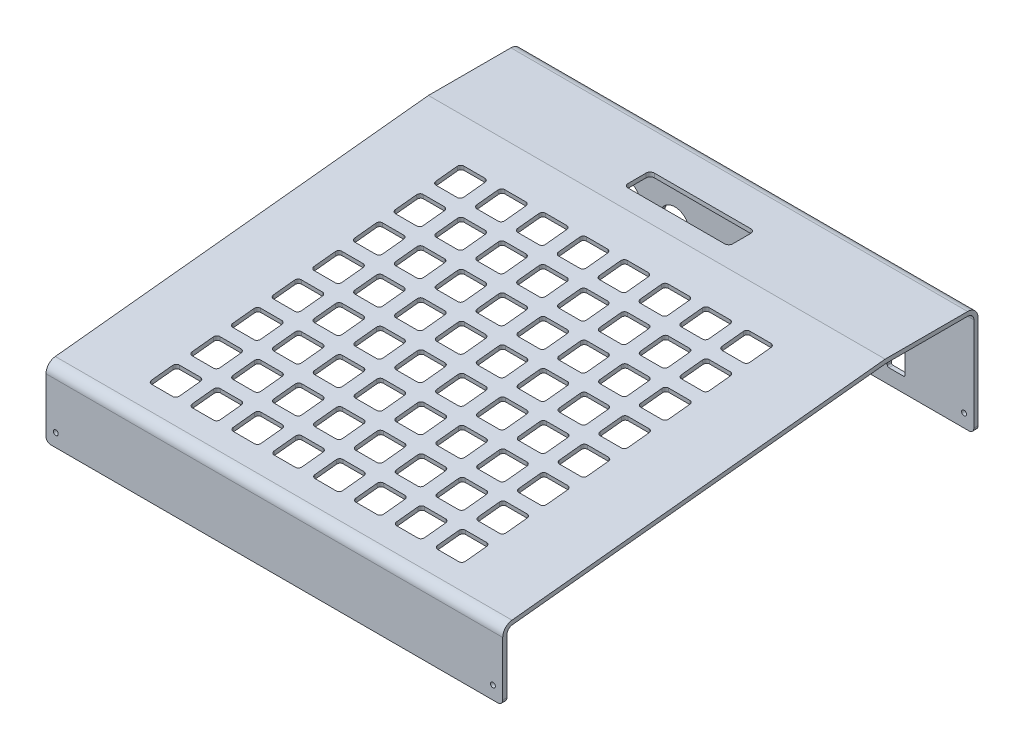
SolidWorks part; units mm, degrees
material "Acrylic (Medium-high impact)"
ref_plane "Front Plane" through (0, 0, 0) normal (0, 0, 1) x (1, 0, 0)
ref_plane "Top Plane" through (0, 0, 0) normal (0, 1, 0) x (1, 0, 0)
ref_plane "Right Plane" through (0, 0, 0) normal (1, 0, 0) x (0, 0, -1)
sketch "Sketch1" plane through (0, 0, 0) normal (1, 0, 0) x (0, 0, -1)
  line L0 (0, 0) -> (0, 84.1309) construction
  line L1 (0, 0) -> (161.7203, 0) construction
  line L2 (-166.9735, -57.6462) -> (123.786, -57.6462)
  line L3 (130.136, -51.2962) -> (130.136, 12.2038)
  line L4 (123.786, 18.5538) -> (66.9711, 18.5538)
  line L5 (66.3027, 18.5185) -> (-167.6419, -6.2448)
  line L6 (-173.3235, -12.5596) -> (-173.3235, -51.2962)
  arc A0 (66.3027, 18.5185) -> (66.9711, 18.5538) centre (66.9711, 12.2038) cw
  arc A1 (123.786, 18.5538) -> (130.136, 12.2038) centre (123.786, 12.2038) cw
  arc A2 (130.136, -51.2962) -> (123.786, -57.6462) centre (123.786, -51.2962) cw
  arc A3 (-166.9735, -57.6462) -> (-173.3235, -51.2962) centre (-166.9735, -51.2962) cw
  arc A4 (-173.3235, -12.5596) -> (-167.6419, -6.2448) centre (-166.9735, -12.5596) cw
  point P11 (66.636, 18.5538)
  point P14 (130.136, 18.5538)
  point P17 (130.136, -57.6462)
  point P20 (-173.3235, -57.6462)
  point P23 (-173.3235, -6.8462)
  dimension "D5" = 6.35
  dimension "D1" = 241.3
  dimension "D2" = 63.5
  dimension "D3" = 76.2
  dimension "D4" = 50.8
sketch "Sketch2" plane through (0, 0, 0) normal (1, 0, 0) x (0, 0, -1)
  line L0 (-166.9735, -54.4712) -> (-166.9735, -18.2729)
  line L1 (-161.2919, -11.9581) -> (66.9711, 12.2038)
  line L2 (66.9711, 12.2038) -> (117.436, 12.2038)
  line L3 (123.786, 5.8538) -> (123.786, -54.4712)
  arc A0 (-161.2919, -11.9581) -> (-166.9735, -18.2729) centre (-160.6235, -18.2729) ccw
  arc A1 (123.786, 5.8538) -> (117.436, 12.2038) centre (117.436, 5.8538) ccw
  point P12 (-166.9735, -12.5596)
  point P15 (123.786, 12.2038)
  dimension "D1" = 6.35
extrude "Extrude-Thin1" add sketch "Sketch2" along normal blind 279.4 thin thin type one direction wall 2.54
sketch "Sketch3" plane through (0, 5.0581, 0.5354) normal (0, 0.9944, 0.1053) x (1, 0, 0)
  line L0 (70.5895, 43.7288) -> (83.5895, 43.7288)
  line L1 (68.5895, 41.7288) -> (68.5895, 28.7288)
  line L2 (45.5895, 43.7288) -> (58.5895, 43.7288)
  line L3 (43.5895, 41.7288) -> (43.5895, 28.7288)
  line L4 (45.5895, 26.7288) -> (58.5895, 26.7288)
  line L5 (70.5895, 26.7288) -> (83.5895, 26.7288)
  line L6 (60.5895, 41.7288) -> (60.5895, 28.7288)
  line L7 (43.5895, 43.7288) -> (60.5895, 26.7288) construction
  line L8 (43.5895, 26.7288) -> (60.5895, 43.7288) construction
  line L9 (85.5895, 41.7288) -> (85.5895, 28.7288)
  line L10 (95.5895, 43.7288) -> (108.5895, 43.7288)
  line L11 (93.5895, 41.7288) -> (93.5895, 28.7288)
  line L12 (95.5895, 26.7288) -> (108.5895, 26.7288)
  line L13 (110.5895, 41.7288) -> (110.5895, 28.7288)
  line L14 (120.5895, 43.7288) -> (133.5895, 43.7288)
  line L15 (118.5895, 41.7288) -> (118.5895, 28.7288)
  line L16 (120.5895, 26.7288) -> (133.5895, 26.7288)
  line L17 (135.5895, 41.7288) -> (135.5895, 28.7288)
  line L18 (145.5895, 43.7288) -> (158.5895, 43.7288)
  line L19 (143.5895, 41.7288) -> (143.5895, 28.7288)
  line L20 (145.5895, 26.7288) -> (158.5895, 26.7288)
  line L21 (160.5895, 41.7288) -> (160.5895, 28.7288)
  line L22 (170.5895, 43.7288) -> (183.5895, 43.7288)
  line L23 (168.5895, 41.7288) -> (168.5895, 28.7288)
  line L24 (170.5895, 26.7288) -> (183.5895, 26.7288)
  line L25 (185.5895, 41.7288) -> (185.5895, 28.7288)
  line L26 (195.5895, 43.7288) -> (208.5895, 43.7288)
  line L27 (193.5895, 41.7288) -> (193.5895, 28.7288)
  line L28 (195.5895, 26.7288) -> (208.5895, 26.7288)
  line L29 (210.5895, 41.7288) -> (210.5895, 28.7288)
  line L30 (220.5895, 43.7288) -> (233.5895, 43.7288)
  line L31 (218.5895, 41.7288) -> (218.5895, 28.7288)
  line L32 (220.5895, 26.7288) -> (233.5895, 26.7288)
  line L33 (235.5895, 41.7288) -> (235.5895, 28.7288)
  line L34 (70.5895, 18.7288) -> (83.5895, 18.7288)
  line L35 (68.5895, 16.7288) -> (68.5895, 3.7288)
  line L36 (70.5895, 1.7288) -> (83.5895, 1.7288)
  line L37 (85.5895, 16.7288) -> (85.5895, 3.7288)
  line L38 (95.5895, 18.7288) -> (108.5895, 18.7288)
  line L39 (93.5895, 16.7288) -> (93.5895, 3.7288)
  line L40 (95.5895, 1.7288) -> (108.5895, 1.7288)
  line L41 (110.5895, 16.7288) -> (110.5895, 3.7288)
  line L42 (120.5895, 18.7288) -> (133.5895, 18.7288)
  line L43 (118.5895, 16.7288) -> (118.5895, 3.7288)
  line L44 (120.5895, 1.7288) -> (133.5895, 1.7288)
  line L45 (135.5895, 16.7288) -> (135.5895, 3.7288)
  line L46 (145.5895, 18.7288) -> (158.5895, 18.7288)
  line L47 (143.5895, 16.7288) -> (143.5895, 3.7288)
  line L48 (145.5895, 1.7288) -> (158.5895, 1.7288)
  line L49 (160.5895, 16.7288) -> (160.5895, 3.7288)
  line L50 (170.5895, 18.7288) -> (183.5895, 18.7288)
  line L51 (168.5895, 16.7288) -> (168.5895, 3.7288)
  line L52 (170.5895, 1.7288) -> (183.5895, 1.7288)
  line L53 (185.5895, 16.7288) -> (185.5895, 3.7288)
  line L54 (195.5895, 18.7288) -> (208.5895, 18.7288)
  line L55 (193.5895, 16.7288) -> (193.5895, 3.7288)
  line L56 (195.5895, 1.7288) -> (208.5895, 1.7288)
  line L57 (210.5895, 16.7288) -> (210.5895, 3.7288)
  line L58 (220.5895, 18.7288) -> (233.5895, 18.7288)
  line L59 (218.5895, 16.7288) -> (218.5895, 3.7288)
  line L60 (220.5895, 1.7288) -> (233.5895, 1.7288)
  line L61 (235.5895, 16.7288) -> (235.5895, 3.7288)
  line L62 (70.5895, -6.2712) -> (83.5895, -6.2712)
  line L63 (68.5895, -8.2712) -> (68.5895, -21.2712)
  line L64 (70.5895, -23.2712) -> (83.5895, -23.2712)
  line L65 (85.5895, -8.2712) -> (85.5895, -21.2712)
  line L66 (95.5895, -6.2712) -> (108.5895, -6.2712)
  line L67 (93.5895, -8.2712) -> (93.5895, -21.2712)
  line L68 (95.5895, -23.2712) -> (108.5895, -23.2712)
  line L69 (110.5895, -8.2712) -> (110.5895, -21.2712)
  line L70 (120.5895, -6.2712) -> (133.5895, -6.2712)
  line L71 (118.5895, -8.2712) -> (118.5895, -21.2712)
  line L72 (120.5895, -23.2712) -> (133.5895, -23.2712)
  line L73 (135.5895, -8.2712) -> (135.5895, -21.2712)
  line L74 (145.5895, -6.2712) -> (158.5895, -6.2712)
  line L75 (143.5895, -8.2712) -> (143.5895, -21.2712)
  line L76 (145.5895, -23.2712) -> (158.5895, -23.2712)
  line L77 (160.5895, -8.2712) -> (160.5895, -21.2712)
  line L78 (170.5895, -6.2712) -> (183.5895, -6.2712)
  line L79 (168.5895, -8.2712) -> (168.5895, -21.2712)
  line L80 (170.5895, -23.2712) -> (183.5895, -23.2712)
  line L81 (185.5895, -8.2712) -> (185.5895, -21.2712)
  line L82 (195.5895, -6.2712) -> (208.5895, -6.2712)
  line L83 (193.5895, -8.2712) -> (193.5895, -21.2712)
  line L84 (195.5895, -23.2712) -> (208.5895, -23.2712)
  line L85 (210.5895, -8.2712) -> (210.5895, -21.2712)
  line L86 (220.5895, -6.2712) -> (233.5895, -6.2712)
  line L87 (218.5895, -8.2712) -> (218.5895, -21.2712)
  line L88 (220.5895, -23.2712) -> (233.5895, -23.2712)
  line L89 (235.5895, -8.2712) -> (235.5895, -21.2712)
  line L90 (70.5895, -31.2712) -> (83.5895, -31.2712)
  line L91 (68.5895, -33.2712) -> (68.5895, -46.2712)
  line L92 (70.5895, -48.2712) -> (83.5895, -48.2712)
  line L93 (85.5895, -33.2712) -> (85.5895, -46.2712)
  line L94 (95.5895, -31.2712) -> (108.5895, -31.2712)
  line L95 (93.5895, -33.2712) -> (93.5895, -46.2712)
  line L96 (95.5895, -48.2712) -> (108.5895, -48.2712)
  line L97 (110.5895, -33.2712) -> (110.5895, -46.2712)
  line L98 (120.5895, -31.2712) -> (133.5895, -31.2712)
  line L99 (118.5895, -33.2712) -> (118.5895, -46.2712)
  line L100 (120.5895, -48.2712) -> (133.5895, -48.2712)
  line L101 (135.5895, -33.2712) -> (135.5895, -46.2712)
  line L102 (145.5895, -31.2712) -> (158.5895, -31.2712)
  line L103 (143.5895, -33.2712) -> (143.5895, -46.2712)
  line L104 (145.5895, -48.2712) -> (158.5895, -48.2712)
  line L105 (160.5895, -33.2712) -> (160.5895, -46.2712)
  line L106 (170.5895, -31.2712) -> (183.5895, -31.2712)
  line L107 (168.5895, -33.2712) -> (168.5895, -46.2712)
  line L108 (170.5895, -48.2712) -> (183.5895, -48.2712)
  line L109 (185.5895, -33.2712) -> (185.5895, -46.2712)
  line L110 (195.5895, -31.2712) -> (208.5895, -31.2712)
  line L111 (193.5895, -33.2712) -> (193.5895, -46.2712)
  line L112 (195.5895, -48.2712) -> (208.5895, -48.2712)
  line L113 (210.5895, -33.2712) -> (210.5895, -46.2712)
  line L114 (220.5895, -31.2712) -> (233.5895, -31.2712)
  line L115 (218.5895, -33.2712) -> (218.5895, -46.2712)
  line L116 (220.5895, -48.2712) -> (233.5895, -48.2712)
  line L117 (235.5895, -33.2712) -> (235.5895, -46.2712)
  line L118 (70.5895, -56.2712) -> (83.5895, -56.2712)
  line L119 (68.5895, -58.2712) -> (68.5895, -71.2712)
  line L120 (70.5895, -73.2712) -> (83.5895, -73.2712)
  line L121 (85.5895, -58.2712) -> (85.5895, -71.2712)
  line L122 (95.5895, -56.2712) -> (108.5895, -56.2712)
  line L123 (93.5895, -58.2712) -> (93.5895, -71.2712)
  line L124 (95.5895, -73.2712) -> (108.5895, -73.2712)
  line L125 (110.5895, -58.2712) -> (110.5895, -71.2712)
  line L126 (120.5895, -56.2712) -> (133.5895, -56.2712)
  line L127 (118.5895, -58.2712) -> (118.5895, -71.2712)
  line L128 (120.5895, -73.2712) -> (133.5895, -73.2712)
  line L129 (135.5895, -58.2712) -> (135.5895, -71.2712)
  line L130 (145.5895, -56.2712) -> (158.5895, -56.2712)
  line L131 (143.5895, -58.2712) -> (143.5895, -71.2712)
  line L132 (145.5895, -73.2712) -> (158.5895, -73.2712)
  line L133 (160.5895, -58.2712) -> (160.5895, -71.2712)
  line L134 (170.5895, -56.2712) -> (183.5895, -56.2712)
  line L135 (168.5895, -58.2712) -> (168.5895, -71.2712)
  line L136 (170.5895, -73.2712) -> (183.5895, -73.2712)
  line L137 (185.5895, -58.2712) -> (185.5895, -71.2712)
  line L138 (195.5895, -56.2712) -> (208.5895, -56.2712)
  line L139 (193.5895, -58.2712) -> (193.5895, -71.2712)
  line L140 (195.5895, -73.2712) -> (208.5895, -73.2712)
  line L141 (210.5895, -58.2712) -> (210.5895, -71.2712)
  line L142 (220.5895, -56.2712) -> (233.5895, -56.2712)
  line L143 (218.5895, -58.2712) -> (218.5895, -71.2712)
  line L144 (220.5895, -73.2712) -> (233.5895, -73.2712)
  line L145 (235.5895, -58.2712) -> (235.5895, -71.2712)
  line L146 (70.5895, -81.2712) -> (83.5895, -81.2712)
  line L147 (68.5895, -83.2712) -> (68.5895, -96.2712)
  line L148 (70.5895, -98.2712) -> (83.5895, -98.2712)
  line L149 (85.5895, -83.2712) -> (85.5895, -96.2712)
  line L150 (95.5895, -81.2712) -> (108.5895, -81.2712)
  line L151 (93.5895, -83.2712) -> (93.5895, -96.2712)
  line L152 (95.5895, -98.2712) -> (108.5895, -98.2712)
  line L153 (110.5895, -83.2712) -> (110.5895, -96.2712)
  line L154 (120.5895, -81.2712) -> (133.5895, -81.2712)
  line L155 (118.5895, -83.2712) -> (118.5895, -96.2712)
  line L156 (120.5895, -98.2712) -> (133.5895, -98.2712)
  line L157 (135.5895, -83.2712) -> (135.5895, -96.2712)
  line L158 (145.5895, -81.2712) -> (158.5895, -81.2712)
  line L159 (143.5895, -83.2712) -> (143.5895, -96.2712)
  line L160 (145.5895, -98.2712) -> (158.5895, -98.2712)
  line L161 (160.5895, -83.2712) -> (160.5895, -96.2712)
  line L162 (170.5895, -81.2712) -> (183.5895, -81.2712)
  line L163 (168.5895, -83.2712) -> (168.5895, -96.2712)
  line L164 (170.5895, -98.2712) -> (183.5895, -98.2712)
  line L165 (185.5895, -83.2712) -> (185.5895, -96.2712)
  line L166 (195.5895, -81.2712) -> (208.5895, -81.2712)
  line L167 (193.5895, -83.2712) -> (193.5895, -96.2712)
  line L168 (195.5895, -98.2712) -> (208.5895, -98.2712)
  line L169 (210.5895, -83.2712) -> (210.5895, -96.2712)
  line L170 (220.5895, -81.2712) -> (233.5895, -81.2712)
  line L171 (218.5895, -83.2712) -> (218.5895, -96.2712)
  line L172 (220.5895, -98.2712) -> (233.5895, -98.2712)
  line L173 (235.5895, -83.2712) -> (235.5895, -96.2712)
  line L174 (70.5895, -106.2712) -> (83.5895, -106.2712)
  line L175 (68.5895, -108.2712) -> (68.5895, -121.2712)
  line L176 (70.5895, -123.2712) -> (83.5895, -123.2712)
  line L177 (85.5895, -108.2712) -> (85.5895, -121.2712)
  line L178 (95.5895, -106.2712) -> (108.5895, -106.2712)
  line L179 (93.5895, -108.2712) -> (93.5895, -121.2712)
  line L180 (95.5895, -123.2712) -> (108.5895, -123.2712)
  line L181 (110.5895, -108.2712) -> (110.5895, -121.2712)
  line L182 (120.5895, -106.2712) -> (133.5895, -106.2712)
  line L183 (118.5895, -108.2712) -> (118.5895, -121.2712)
  line L184 (120.5895, -123.2712) -> (133.5895, -123.2712)
  line L185 (135.5895, -108.2712) -> (135.5895, -121.2712)
  line L186 (145.5895, -106.2712) -> (158.5895, -106.2712)
  line L187 (143.5895, -108.2712) -> (143.5895, -121.2712)
  line L188 (145.5895, -123.2712) -> (158.5895, -123.2712)
  line L189 (160.5895, -108.2712) -> (160.5895, -121.2712)
  line L190 (170.5895, -106.2712) -> (183.5895, -106.2712)
  line L191 (168.5895, -108.2712) -> (168.5895, -121.2712)
  line L192 (170.5895, -123.2712) -> (183.5895, -123.2712)
  line L193 (185.5895, -108.2712) -> (185.5895, -121.2712)
  line L194 (195.5895, -106.2712) -> (208.5895, -106.2712)
  line L195 (193.5895, -108.2712) -> (193.5895, -121.2712)
  line L196 (195.5895, -123.2712) -> (208.5895, -123.2712)
  line L197 (210.5895, -108.2712) -> (210.5895, -121.2712)
  line L198 (220.5895, -106.2712) -> (233.5895, -106.2712)
  line L199 (218.5895, -108.2712) -> (218.5895, -121.2712)
  line L200 (220.5895, -123.2712) -> (233.5895, -123.2712)
  line L201 (235.5895, -108.2712) -> (235.5895, -121.2712)
  line L202 (70.5895, -131.2712) -> (83.5895, -131.2712)
  line L203 (68.5895, -133.2712) -> (68.5895, -146.2712)
  line L204 (70.5895, -148.2712) -> (83.5895, -148.2712)
  line L205 (85.5895, -133.2712) -> (85.5895, -146.2712)
  line L206 (95.5895, -131.2712) -> (108.5895, -131.2712)
  line L207 (93.5895, -133.2712) -> (93.5895, -146.2712)
  line L208 (95.5895, -148.2712) -> (108.5895, -148.2712)
  line L209 (110.5895, -133.2712) -> (110.5895, -146.2712)
  line L210 (120.5895, -131.2712) -> (133.5895, -131.2712)
  line L211 (118.5895, -133.2712) -> (118.5895, -146.2712)
  line L212 (120.5895, -148.2712) -> (133.5895, -148.2712)
  line L213 (135.5895, -133.2712) -> (135.5895, -146.2712)
  line L214 (145.5895, -131.2712) -> (158.5895, -131.2712)
  line L215 (143.5895, -133.2712) -> (143.5895, -146.2712)
  line L216 (145.5895, -148.2712) -> (158.5895, -148.2712)
  line L217 (160.5895, -133.2712) -> (160.5895, -146.2712)
  line L218 (170.5895, -131.2712) -> (183.5895, -131.2712)
  line L219 (168.5895, -133.2712) -> (168.5895, -146.2712)
  line L220 (170.5895, -148.2712) -> (183.5895, -148.2712)
  line L221 (185.5895, -133.2712) -> (185.5895, -146.2712)
  line L222 (195.5895, -131.2712) -> (208.5895, -131.2712)
  line L223 (193.5895, -133.2712) -> (193.5895, -146.2712)
  line L224 (195.5895, -148.2712) -> (208.5895, -148.2712)
  line L225 (210.5895, -133.2712) -> (210.5895, -146.2712)
  line L226 (220.5895, -131.2712) -> (233.5895, -131.2712)
  line L227 (218.5895, -133.2712) -> (218.5895, -146.2712)
  line L228 (220.5895, -148.2712) -> (233.5895, -148.2712)
  line L229 (235.5895, -133.2712) -> (235.5895, -146.2712)
  line L230 (45.5895, 18.7288) -> (58.5895, 18.7288)
  line L231 (43.5895, 16.7288) -> (43.5895, 3.7288)
  line L232 (45.5895, 1.7288) -> (58.5895, 1.7288)
  line L233 (60.5895, 16.7288) -> (60.5895, 3.7288)
  line L234 (45.5895, -6.2712) -> (58.5895, -6.2712)
  line L235 (43.5895, -8.2712) -> (43.5895, -21.2712)
  line L236 (45.5895, -23.2712) -> (58.5895, -23.2712)
  line L237 (60.5895, -8.2712) -> (60.5895, -21.2712)
  line L238 (45.5895, -31.2712) -> (58.5895, -31.2712)
  line L239 (43.5895, -33.2712) -> (43.5895, -46.2712)
  line L240 (45.5895, -48.2712) -> (58.5895, -48.2712)
  line L241 (60.5895, -33.2712) -> (60.5895, -46.2712)
  line L242 (45.5895, -56.2712) -> (58.5895, -56.2712)
  line L243 (43.5895, -58.2712) -> (43.5895, -71.2712)
  line L244 (45.5895, -73.2712) -> (58.5895, -73.2712)
  line L245 (60.5895, -58.2712) -> (60.5895, -71.2712)
  line L246 (45.5895, -81.2712) -> (58.5895, -81.2712)
  line L247 (43.5895, -83.2712) -> (43.5895, -96.2712)
  line L248 (45.5895, -98.2712) -> (58.5895, -98.2712)
  line L249 (60.5895, -83.2712) -> (60.5895, -96.2712)
  line L250 (45.5895, -106.2712) -> (58.5895, -106.2712)
  line L251 (43.5895, -108.2712) -> (43.5895, -121.2712)
  line L252 (45.5895, -123.2712) -> (58.5895, -123.2712)
  line L253 (60.5895, -108.2712) -> (60.5895, -121.2712)
  line L254 (45.5895, -131.2712) -> (58.5895, -131.2712)
  line L255 (43.5895, -133.2712) -> (43.5895, -146.2712)
  line L256 (45.5895, -148.2712) -> (58.5895, -148.2712)
  line L257 (60.5895, -133.2712) -> (60.5895, -146.2712)
  line L258 (139.7, 123.7497) -> (139.7, -161.6546) construction
  line L259 (279.4, 123.7497) -> (0, 123.7497) construction
  line L260 (279.4, -161.6546) -> (0, -161.6546) construction
  arc A0 (58.5895, 43.7288) -> (60.5895, 41.7288) centre (58.5895, 41.7288) cw
  arc A1 (60.5895, 28.7288) -> (58.5895, 26.7288) centre (58.5895, 28.7288) cw
  arc A2 (45.5895, 26.7288) -> (43.5895, 28.7288) centre (45.5895, 28.7288) cw
  arc A3 (43.5895, 41.7288) -> (45.5895, 43.7288) centre (45.5895, 41.7288) cw
  arc A4 (68.5895, 41.7288) -> (70.5895, 43.7288) centre (70.5895, 41.7288) cw
  arc A5 (70.5895, 26.7288) -> (68.5895, 28.7288) centre (70.5895, 28.7288) cw
  arc A6 (85.5895, 28.7288) -> (83.5895, 26.7288) centre (83.5895, 28.7288) cw
  arc A7 (83.5895, 43.7288) -> (85.5895, 41.7288) centre (83.5895, 41.7288) cw
  arc A8 (93.5895, 41.7288) -> (95.5895, 43.7288) centre (95.5895, 41.7288) cw
  arc A9 (95.5895, 26.7288) -> (93.5895, 28.7288) centre (95.5895, 28.7288) cw
  arc A10 (110.5895, 28.7288) -> (108.5895, 26.7288) centre (108.5895, 28.7288) cw
  arc A11 (108.5895, 43.7288) -> (110.5895, 41.7288) centre (108.5895, 41.7288) cw
  arc A12 (118.5895, 41.7288) -> (120.5895, 43.7288) centre (120.5895, 41.7288) cw
  arc A13 (120.5895, 26.7288) -> (118.5895, 28.7288) centre (120.5895, 28.7288) cw
  arc A14 (135.5895, 28.7288) -> (133.5895, 26.7288) centre (133.5895, 28.7288) cw
  arc A15 (133.5895, 43.7288) -> (135.5895, 41.7288) centre (133.5895, 41.7288) cw
  arc A16 (143.5895, 41.7288) -> (145.5895, 43.7288) centre (145.5895, 41.7288) cw
  arc A17 (145.5895, 26.7288) -> (143.5895, 28.7288) centre (145.5895, 28.7288) cw
  arc A18 (160.5895, 28.7288) -> (158.5895, 26.7288) centre (158.5895, 28.7288) cw
  arc A19 (158.5895, 43.7288) -> (160.5895, 41.7288) centre (158.5895, 41.7288) cw
  arc A20 (168.5895, 41.7288) -> (170.5895, 43.7288) centre (170.5895, 41.7288) cw
  arc A21 (170.5895, 26.7288) -> (168.5895, 28.7288) centre (170.5895, 28.7288) cw
  arc A22 (185.5895, 28.7288) -> (183.5895, 26.7288) centre (183.5895, 28.7288) cw
  arc A23 (183.5895, 43.7288) -> (185.5895, 41.7288) centre (183.5895, 41.7288) cw
  arc A24 (193.5895, 41.7288) -> (195.5895, 43.7288) centre (195.5895, 41.7288) cw
  arc A25 (195.5895, 26.7288) -> (193.5895, 28.7288) centre (195.5895, 28.7288) cw
  arc A26 (210.5895, 28.7288) -> (208.5895, 26.7288) centre (208.5895, 28.7288) cw
  arc A27 (208.5895, 43.7288) -> (210.5895, 41.7288) centre (208.5895, 41.7288) cw
  arc A28 (218.5895, 41.7288) -> (220.5895, 43.7288) centre (220.5895, 41.7288) cw
  arc A29 (220.5895, 26.7288) -> (218.5895, 28.7288) centre (220.5895, 28.7288) cw
  arc A30 (235.5895, 28.7288) -> (233.5895, 26.7288) centre (233.5895, 28.7288) cw
  arc A31 (233.5895, 43.7288) -> (235.5895, 41.7288) centre (233.5895, 41.7288) cw
  arc A32 (68.5895, 16.7288) -> (70.5895, 18.7288) centre (70.5895, 16.7288) cw
  arc A33 (70.5895, 1.7288) -> (68.5895, 3.7288) centre (70.5895, 3.7288) cw
  arc A34 (85.5895, 3.7288) -> (83.5895, 1.7288) centre (83.5895, 3.7288) cw
  arc A35 (83.5895, 18.7288) -> (85.5895, 16.7288) centre (83.5895, 16.7288) cw
  arc A36 (93.5895, 16.7288) -> (95.5895, 18.7288) centre (95.5895, 16.7288) cw
  arc A37 (95.5895, 1.7288) -> (93.5895, 3.7288) centre (95.5895, 3.7288) cw
  arc A38 (110.5895, 3.7288) -> (108.5895, 1.7288) centre (108.5895, 3.7288) cw
  arc A39 (108.5895, 18.7288) -> (110.5895, 16.7288) centre (108.5895, 16.7288) cw
  arc A40 (118.5895, 16.7288) -> (120.5895, 18.7288) centre (120.5895, 16.7288) cw
  arc A41 (120.5895, 1.7288) -> (118.5895, 3.7288) centre (120.5895, 3.7288) cw
  arc A42 (135.5895, 3.7288) -> (133.5895, 1.7288) centre (133.5895, 3.7288) cw
  arc A43 (133.5895, 18.7288) -> (135.5895, 16.7288) centre (133.5895, 16.7288) cw
  arc A44 (143.5895, 16.7288) -> (145.5895, 18.7288) centre (145.5895, 16.7288) cw
  arc A45 (145.5895, 1.7288) -> (143.5895, 3.7288) centre (145.5895, 3.7288) cw
  arc A46 (160.5895, 3.7288) -> (158.5895, 1.7288) centre (158.5895, 3.7288) cw
  arc A47 (158.5895, 18.7288) -> (160.5895, 16.7288) centre (158.5895, 16.7288) cw
  arc A48 (168.5895, 16.7288) -> (170.5895, 18.7288) centre (170.5895, 16.7288) cw
  arc A49 (170.5895, 1.7288) -> (168.5895, 3.7288) centre (170.5895, 3.7288) cw
  arc A50 (185.5895, 3.7288) -> (183.5895, 1.7288) centre (183.5895, 3.7288) cw
  arc A51 (183.5895, 18.7288) -> (185.5895, 16.7288) centre (183.5895, 16.7288) cw
  arc A52 (193.5895, 16.7288) -> (195.5895, 18.7288) centre (195.5895, 16.7288) cw
  arc A53 (195.5895, 1.7288) -> (193.5895, 3.7288) centre (195.5895, 3.7288) cw
  arc A54 (210.5895, 3.7288) -> (208.5895, 1.7288) centre (208.5895, 3.7288) cw
  arc A55 (208.5895, 18.7288) -> (210.5895, 16.7288) centre (208.5895, 16.7288) cw
  arc A56 (218.5895, 16.7288) -> (220.5895, 18.7288) centre (220.5895, 16.7288) cw
  arc A57 (220.5895, 1.7288) -> (218.5895, 3.7288) centre (220.5895, 3.7288) cw
  arc A58 (235.5895, 3.7288) -> (233.5895, 1.7288) centre (233.5895, 3.7288) cw
  arc A59 (233.5895, 18.7288) -> (235.5895, 16.7288) centre (233.5895, 16.7288) cw
  arc A60 (68.5895, -8.2712) -> (70.5895, -6.2712) centre (70.5895, -8.2712) cw
  arc A61 (70.5895, -23.2712) -> (68.5895, -21.2712) centre (70.5895, -21.2712) cw
  arc A62 (85.5895, -21.2712) -> (83.5895, -23.2712) centre (83.5895, -21.2712) cw
  arc A63 (83.5895, -6.2712) -> (85.5895, -8.2712) centre (83.5895, -8.2712) cw
  arc A64 (93.5895, -8.2712) -> (95.5895, -6.2712) centre (95.5895, -8.2712) cw
  arc A65 (95.5895, -23.2712) -> (93.5895, -21.2712) centre (95.5895, -21.2712) cw
  arc A66 (110.5895, -21.2712) -> (108.5895, -23.2712) centre (108.5895, -21.2712) cw
  arc A67 (108.5895, -6.2712) -> (110.5895, -8.2712) centre (108.5895, -8.2712) cw
  arc A68 (118.5895, -8.2712) -> (120.5895, -6.2712) centre (120.5895, -8.2712) cw
  arc A69 (120.5895, -23.2712) -> (118.5895, -21.2712) centre (120.5895, -21.2712) cw
  arc A70 (135.5895, -21.2712) -> (133.5895, -23.2712) centre (133.5895, -21.2712) cw
  arc A71 (133.5895, -6.2712) -> (135.5895, -8.2712) centre (133.5895, -8.2712) cw
  arc A72 (143.5895, -8.2712) -> (145.5895, -6.2712) centre (145.5895, -8.2712) cw
  arc A73 (145.5895, -23.2712) -> (143.5895, -21.2712) centre (145.5895, -21.2712) cw
  arc A74 (160.5895, -21.2712) -> (158.5895, -23.2712) centre (158.5895, -21.2712) cw
  arc A75 (158.5895, -6.2712) -> (160.5895, -8.2712) centre (158.5895, -8.2712) cw
  arc A76 (168.5895, -8.2712) -> (170.5895, -6.2712) centre (170.5895, -8.2712) cw
  arc A77 (170.5895, -23.2712) -> (168.5895, -21.2712) centre (170.5895, -21.2712) cw
  arc A78 (185.5895, -21.2712) -> (183.5895, -23.2712) centre (183.5895, -21.2712) cw
  arc A79 (183.5895, -6.2712) -> (185.5895, -8.2712) centre (183.5895, -8.2712) cw
  arc A80 (193.5895, -8.2712) -> (195.5895, -6.2712) centre (195.5895, -8.2712) cw
  arc A81 (195.5895, -23.2712) -> (193.5895, -21.2712) centre (195.5895, -21.2712) cw
  arc A82 (210.5895, -21.2712) -> (208.5895, -23.2712) centre (208.5895, -21.2712) cw
  arc A83 (208.5895, -6.2712) -> (210.5895, -8.2712) centre (208.5895, -8.2712) cw
  arc A84 (218.5895, -8.2712) -> (220.5895, -6.2712) centre (220.5895, -8.2712) cw
  arc A85 (220.5895, -23.2712) -> (218.5895, -21.2712) centre (220.5895, -21.2712) cw
  arc A86 (235.5895, -21.2712) -> (233.5895, -23.2712) centre (233.5895, -21.2712) cw
  arc A87 (233.5895, -6.2712) -> (235.5895, -8.2712) centre (233.5895, -8.2712) cw
  arc A88 (68.5895, -33.2712) -> (70.5895, -31.2712) centre (70.5895, -33.2712) cw
  arc A89 (70.5895, -48.2712) -> (68.5895, -46.2712) centre (70.5895, -46.2712) cw
  arc A90 (85.5895, -46.2712) -> (83.5895, -48.2712) centre (83.5895, -46.2712) cw
  arc A91 (83.5895, -31.2712) -> (85.5895, -33.2712) centre (83.5895, -33.2712) cw
  arc A92 (93.5895, -33.2712) -> (95.5895, -31.2712) centre (95.5895, -33.2712) cw
  arc A93 (95.5895, -48.2712) -> (93.5895, -46.2712) centre (95.5895, -46.2712) cw
  arc A94 (110.5895, -46.2712) -> (108.5895, -48.2712) centre (108.5895, -46.2712) cw
  arc A95 (108.5895, -31.2712) -> (110.5895, -33.2712) centre (108.5895, -33.2712) cw
  arc A96 (118.5895, -33.2712) -> (120.5895, -31.2712) centre (120.5895, -33.2712) cw
  arc A97 (120.5895, -48.2712) -> (118.5895, -46.2712) centre (120.5895, -46.2712) cw
  arc A98 (135.5895, -46.2712) -> (133.5895, -48.2712) centre (133.5895, -46.2712) cw
  arc A99 (133.5895, -31.2712) -> (135.5895, -33.2712) centre (133.5895, -33.2712) cw
  arc A100 (143.5895, -33.2712) -> (145.5895, -31.2712) centre (145.5895, -33.2712) cw
  arc A101 (145.5895, -48.2712) -> (143.5895, -46.2712) centre (145.5895, -46.2712) cw
  arc A102 (160.5895, -46.2712) -> (158.5895, -48.2712) centre (158.5895, -46.2712) cw
  arc A103 (158.5895, -31.2712) -> (160.5895, -33.2712) centre (158.5895, -33.2712) cw
  arc A104 (168.5895, -33.2712) -> (170.5895, -31.2712) centre (170.5895, -33.2712) cw
  arc A105 (170.5895, -48.2712) -> (168.5895, -46.2712) centre (170.5895, -46.2712) cw
  arc A106 (185.5895, -46.2712) -> (183.5895, -48.2712) centre (183.5895, -46.2712) cw
  arc A107 (183.5895, -31.2712) -> (185.5895, -33.2712) centre (183.5895, -33.2712) cw
  arc A108 (193.5895, -33.2712) -> (195.5895, -31.2712) centre (195.5895, -33.2712) cw
  arc A109 (195.5895, -48.2712) -> (193.5895, -46.2712) centre (195.5895, -46.2712) cw
  arc A110 (210.5895, -46.2712) -> (208.5895, -48.2712) centre (208.5895, -46.2712) cw
  arc A111 (208.5895, -31.2712) -> (210.5895, -33.2712) centre (208.5895, -33.2712) cw
  arc A112 (218.5895, -33.2712) -> (220.5895, -31.2712) centre (220.5895, -33.2712) cw
  arc A113 (220.5895, -48.2712) -> (218.5895, -46.2712) centre (220.5895, -46.2712) cw
  arc A114 (235.5895, -46.2712) -> (233.5895, -48.2712) centre (233.5895, -46.2712) cw
  arc A115 (233.5895, -31.2712) -> (235.5895, -33.2712) centre (233.5895, -33.2712) cw
  arc A116 (68.5895, -58.2712) -> (70.5895, -56.2712) centre (70.5895, -58.2712) cw
  arc A117 (70.5895, -73.2712) -> (68.5895, -71.2712) centre (70.5895, -71.2712) cw
  arc A118 (85.5895, -71.2712) -> (83.5895, -73.2712) centre (83.5895, -71.2712) cw
  arc A119 (83.5895, -56.2712) -> (85.5895, -58.2712) centre (83.5895, -58.2712) cw
  arc A120 (93.5895, -58.2712) -> (95.5895, -56.2712) centre (95.5895, -58.2712) cw
  arc A121 (95.5895, -73.2712) -> (93.5895, -71.2712) centre (95.5895, -71.2712) cw
  arc A122 (110.5895, -71.2712) -> (108.5895, -73.2712) centre (108.5895, -71.2712) cw
  arc A123 (108.5895, -56.2712) -> (110.5895, -58.2712) centre (108.5895, -58.2712) cw
  arc A124 (118.5895, -58.2712) -> (120.5895, -56.2712) centre (120.5895, -58.2712) cw
  arc A125 (120.5895, -73.2712) -> (118.5895, -71.2712) centre (120.5895, -71.2712) cw
  arc A126 (135.5895, -71.2712) -> (133.5895, -73.2712) centre (133.5895, -71.2712) cw
  arc A127 (133.5895, -56.2712) -> (135.5895, -58.2712) centre (133.5895, -58.2712) cw
  arc A128 (143.5895, -58.2712) -> (145.5895, -56.2712) centre (145.5895, -58.2712) cw
  arc A129 (145.5895, -73.2712) -> (143.5895, -71.2712) centre (145.5895, -71.2712) cw
  arc A130 (160.5895, -71.2712) -> (158.5895, -73.2712) centre (158.5895, -71.2712) cw
  arc A131 (158.5895, -56.2712) -> (160.5895, -58.2712) centre (158.5895, -58.2712) cw
  arc A132 (168.5895, -58.2712) -> (170.5895, -56.2712) centre (170.5895, -58.2712) cw
  arc A133 (170.5895, -73.2712) -> (168.5895, -71.2712) centre (170.5895, -71.2712) cw
  arc A134 (185.5895, -71.2712) -> (183.5895, -73.2712) centre (183.5895, -71.2712) cw
  arc A135 (183.5895, -56.2712) -> (185.5895, -58.2712) centre (183.5895, -58.2712) cw
  arc A136 (193.5895, -58.2712) -> (195.5895, -56.2712) centre (195.5895, -58.2712) cw
  arc A137 (195.5895, -73.2712) -> (193.5895, -71.2712) centre (195.5895, -71.2712) cw
  arc A138 (210.5895, -71.2712) -> (208.5895, -73.2712) centre (208.5895, -71.2712) cw
  arc A139 (208.5895, -56.2712) -> (210.5895, -58.2712) centre (208.5895, -58.2712) cw
  arc A140 (218.5895, -58.2712) -> (220.5895, -56.2712) centre (220.5895, -58.2712) cw
  arc A141 (220.5895, -73.2712) -> (218.5895, -71.2712) centre (220.5895, -71.2712) cw
  arc A142 (235.5895, -71.2712) -> (233.5895, -73.2712) centre (233.5895, -71.2712) cw
  arc A143 (233.5895, -56.2712) -> (235.5895, -58.2712) centre (233.5895, -58.2712) cw
  arc A144 (68.5895, -83.2712) -> (70.5895, -81.2712) centre (70.5895, -83.2712) cw
  arc A145 (70.5895, -98.2712) -> (68.5895, -96.2712) centre (70.5895, -96.2712) cw
  arc A146 (85.5895, -96.2712) -> (83.5895, -98.2712) centre (83.5895, -96.2712) cw
  arc A147 (83.5895, -81.2712) -> (85.5895, -83.2712) centre (83.5895, -83.2712) cw
  arc A148 (93.5895, -83.2712) -> (95.5895, -81.2712) centre (95.5895, -83.2712) cw
  arc A149 (95.5895, -98.2712) -> (93.5895, -96.2712) centre (95.5895, -96.2712) cw
  arc A150 (110.5895, -96.2712) -> (108.5895, -98.2712) centre (108.5895, -96.2712) cw
  arc A151 (108.5895, -81.2712) -> (110.5895, -83.2712) centre (108.5895, -83.2712) cw
  arc A152 (118.5895, -83.2712) -> (120.5895, -81.2712) centre (120.5895, -83.2712) cw
  arc A153 (120.5895, -98.2712) -> (118.5895, -96.2712) centre (120.5895, -96.2712) cw
  arc A154 (135.5895, -96.2712) -> (133.5895, -98.2712) centre (133.5895, -96.2712) cw
  arc A155 (133.5895, -81.2712) -> (135.5895, -83.2712) centre (133.5895, -83.2712) cw
  arc A156 (143.5895, -83.2712) -> (145.5895, -81.2712) centre (145.5895, -83.2712) cw
  arc A157 (145.5895, -98.2712) -> (143.5895, -96.2712) centre (145.5895, -96.2712) cw
  arc A158 (160.5895, -96.2712) -> (158.5895, -98.2712) centre (158.5895, -96.2712) cw
  arc A159 (158.5895, -81.2712) -> (160.5895, -83.2712) centre (158.5895, -83.2712) cw
  arc A160 (168.5895, -83.2712) -> (170.5895, -81.2712) centre (170.5895, -83.2712) cw
  arc A161 (170.5895, -98.2712) -> (168.5895, -96.2712) centre (170.5895, -96.2712) cw
  arc A162 (185.5895, -96.2712) -> (183.5895, -98.2712) centre (183.5895, -96.2712) cw
  arc A163 (183.5895, -81.2712) -> (185.5895, -83.2712) centre (183.5895, -83.2712) cw
  arc A164 (193.5895, -83.2712) -> (195.5895, -81.2712) centre (195.5895, -83.2712) cw
  arc A165 (195.5895, -98.2712) -> (193.5895, -96.2712) centre (195.5895, -96.2712) cw
  arc A166 (210.5895, -96.2712) -> (208.5895, -98.2712) centre (208.5895, -96.2712) cw
  arc A167 (208.5895, -81.2712) -> (210.5895, -83.2712) centre (208.5895, -83.2712) cw
  arc A168 (218.5895, -83.2712) -> (220.5895, -81.2712) centre (220.5895, -83.2712) cw
  arc A169 (220.5895, -98.2712) -> (218.5895, -96.2712) centre (220.5895, -96.2712) cw
  arc A170 (235.5895, -96.2712) -> (233.5895, -98.2712) centre (233.5895, -96.2712) cw
  arc A171 (233.5895, -81.2712) -> (235.5895, -83.2712) centre (233.5895, -83.2712) cw
  arc A172 (68.5895, -108.2712) -> (70.5895, -106.2712) centre (70.5895, -108.2712) cw
  arc A173 (70.5895, -123.2712) -> (68.5895, -121.2712) centre (70.5895, -121.2712) cw
  arc A174 (85.5895, -121.2712) -> (83.5895, -123.2712) centre (83.5895, -121.2712) cw
  arc A175 (83.5895, -106.2712) -> (85.5895, -108.2712) centre (83.5895, -108.2712) cw
  arc A176 (93.5895, -108.2712) -> (95.5895, -106.2712) centre (95.5895, -108.2712) cw
  arc A177 (95.5895, -123.2712) -> (93.5895, -121.2712) centre (95.5895, -121.2712) cw
  arc A178 (110.5895, -121.2712) -> (108.5895, -123.2712) centre (108.5895, -121.2712) cw
  arc A179 (108.5895, -106.2712) -> (110.5895, -108.2712) centre (108.5895, -108.2712) cw
  arc A180 (118.5895, -108.2712) -> (120.5895, -106.2712) centre (120.5895, -108.2712) cw
  arc A181 (120.5895, -123.2712) -> (118.5895, -121.2712) centre (120.5895, -121.2712) cw
  arc A182 (135.5895, -121.2712) -> (133.5895, -123.2712) centre (133.5895, -121.2712) cw
  arc A183 (133.5895, -106.2712) -> (135.5895, -108.2712) centre (133.5895, -108.2712) cw
  arc A184 (143.5895, -108.2712) -> (145.5895, -106.2712) centre (145.5895, -108.2712) cw
  arc A185 (145.5895, -123.2712) -> (143.5895, -121.2712) centre (145.5895, -121.2712) cw
  arc A186 (160.5895, -121.2712) -> (158.5895, -123.2712) centre (158.5895, -121.2712) cw
  arc A187 (158.5895, -106.2712) -> (160.5895, -108.2712) centre (158.5895, -108.2712) cw
  arc A188 (168.5895, -108.2712) -> (170.5895, -106.2712) centre (170.5895, -108.2712) cw
  arc A189 (170.5895, -123.2712) -> (168.5895, -121.2712) centre (170.5895, -121.2712) cw
  arc A190 (185.5895, -121.2712) -> (183.5895, -123.2712) centre (183.5895, -121.2712) cw
  arc A191 (183.5895, -106.2712) -> (185.5895, -108.2712) centre (183.5895, -108.2712) cw
  arc A192 (193.5895, -108.2712) -> (195.5895, -106.2712) centre (195.5895, -108.2712) cw
  arc A193 (195.5895, -123.2712) -> (193.5895, -121.2712) centre (195.5895, -121.2712) cw
  arc A194 (210.5895, -121.2712) -> (208.5895, -123.2712) centre (208.5895, -121.2712) cw
  arc A195 (208.5895, -106.2712) -> (210.5895, -108.2712) centre (208.5895, -108.2712) cw
  arc A196 (218.5895, -108.2712) -> (220.5895, -106.2712) centre (220.5895, -108.2712) cw
  arc A197 (220.5895, -123.2712) -> (218.5895, -121.2712) centre (220.5895, -121.2712) cw
  arc A198 (235.5895, -121.2712) -> (233.5895, -123.2712) centre (233.5895, -121.2712) cw
  arc A199 (233.5895, -106.2712) -> (235.5895, -108.2712) centre (233.5895, -108.2712) cw
  arc A200 (68.5895, -133.2712) -> (70.5895, -131.2712) centre (70.5895, -133.2712) cw
  arc A201 (70.5895, -148.2712) -> (68.5895, -146.2712) centre (70.5895, -146.2712) cw
  arc A202 (85.5895, -146.2712) -> (83.5895, -148.2712) centre (83.5895, -146.2712) cw
  arc A203 (83.5895, -131.2712) -> (85.5895, -133.2712) centre (83.5895, -133.2712) cw
  arc A204 (93.5895, -133.2712) -> (95.5895, -131.2712) centre (95.5895, -133.2712) cw
  arc A205 (95.5895, -148.2712) -> (93.5895, -146.2712) centre (95.5895, -146.2712) cw
  arc A206 (110.5895, -146.2712) -> (108.5895, -148.2712) centre (108.5895, -146.2712) cw
  arc A207 (108.5895, -131.2712) -> (110.5895, -133.2712) centre (108.5895, -133.2712) cw
  arc A208 (118.5895, -133.2712) -> (120.5895, -131.2712) centre (120.5895, -133.2712) cw
  arc A209 (120.5895, -148.2712) -> (118.5895, -146.2712) centre (120.5895, -146.2712) cw
  arc A210 (135.5895, -146.2712) -> (133.5895, -148.2712) centre (133.5895, -146.2712) cw
  arc A211 (133.5895, -131.2712) -> (135.5895, -133.2712) centre (133.5895, -133.2712) cw
  arc A212 (143.5895, -133.2712) -> (145.5895, -131.2712) centre (145.5895, -133.2712) cw
  arc A213 (145.5895, -148.2712) -> (143.5895, -146.2712) centre (145.5895, -146.2712) cw
  arc A214 (160.5895, -146.2712) -> (158.5895, -148.2712) centre (158.5895, -146.2712) cw
  arc A215 (158.5895, -131.2712) -> (160.5895, -133.2712) centre (158.5895, -133.2712) cw
  arc A216 (168.5895, -133.2712) -> (170.5895, -131.2712) centre (170.5895, -133.2712) cw
  arc A217 (170.5895, -148.2712) -> (168.5895, -146.2712) centre (170.5895, -146.2712) cw
  arc A218 (185.5895, -146.2712) -> (183.5895, -148.2712) centre (183.5895, -146.2712) cw
  arc A219 (183.5895, -131.2712) -> (185.5895, -133.2712) centre (183.5895, -133.2712) cw
  arc A220 (193.5895, -133.2712) -> (195.5895, -131.2712) centre (195.5895, -133.2712) cw
  arc A221 (195.5895, -148.2712) -> (193.5895, -146.2712) centre (195.5895, -146.2712) cw
  arc A222 (210.5895, -146.2712) -> (208.5895, -148.2712) centre (208.5895, -146.2712) cw
  arc A223 (208.5895, -131.2712) -> (210.5895, -133.2712) centre (208.5895, -133.2712) cw
  arc A224 (218.5895, -133.2712) -> (220.5895, -131.2712) centre (220.5895, -133.2712) cw
  arc A225 (220.5895, -148.2712) -> (218.5895, -146.2712) centre (220.5895, -146.2712) cw
  arc A226 (235.5895, -146.2712) -> (233.5895, -148.2712) centre (233.5895, -146.2712) cw
  arc A227 (233.5895, -131.2712) -> (235.5895, -133.2712) centre (233.5895, -133.2712) cw
  arc A228 (43.5895, 16.7288) -> (45.5895, 18.7288) centre (45.5895, 16.7288) cw
  arc A229 (45.5895, 1.7288) -> (43.5895, 3.7288) centre (45.5895, 3.7288) cw
  arc A230 (60.5895, 3.7288) -> (58.5895, 1.7288) centre (58.5895, 3.7288) cw
  arc A231 (58.5895, 18.7288) -> (60.5895, 16.7288) centre (58.5895, 16.7288) cw
  arc A232 (43.5895, -8.2712) -> (45.5895, -6.2712) centre (45.5895, -8.2712) cw
  arc A233 (45.5895, -23.2712) -> (43.5895, -21.2712) centre (45.5895, -21.2712) cw
  arc A234 (60.5895, -21.2712) -> (58.5895, -23.2712) centre (58.5895, -21.2712) cw
  arc A235 (58.5895, -6.2712) -> (60.5895, -8.2712) centre (58.5895, -8.2712) cw
  arc A236 (43.5895, -33.2712) -> (45.5895, -31.2712) centre (45.5895, -33.2712) cw
  arc A237 (45.5895, -48.2712) -> (43.5895, -46.2712) centre (45.5895, -46.2712) cw
  arc A238 (60.5895, -46.2712) -> (58.5895, -48.2712) centre (58.5895, -46.2712) cw
  arc A239 (58.5895, -31.2712) -> (60.5895, -33.2712) centre (58.5895, -33.2712) cw
  arc A240 (43.5895, -58.2712) -> (45.5895, -56.2712) centre (45.5895, -58.2712) cw
  arc A241 (45.5895, -73.2712) -> (43.5895, -71.2712) centre (45.5895, -71.2712) cw
  arc A242 (60.5895, -71.2712) -> (58.5895, -73.2712) centre (58.5895, -71.2712) cw
  arc A243 (58.5895, -56.2712) -> (60.5895, -58.2712) centre (58.5895, -58.2712) cw
  arc A244 (43.5895, -83.2712) -> (45.5895, -81.2712) centre (45.5895, -83.2712) cw
  arc A245 (45.5895, -98.2712) -> (43.5895, -96.2712) centre (45.5895, -96.2712) cw
  arc A246 (60.5895, -96.2712) -> (58.5895, -98.2712) centre (58.5895, -96.2712) cw
  arc A247 (58.5895, -81.2712) -> (60.5895, -83.2712) centre (58.5895, -83.2712) cw
  arc A248 (43.5895, -108.2712) -> (45.5895, -106.2712) centre (45.5895, -108.2712) cw
  arc A249 (45.5895, -123.2712) -> (43.5895, -121.2712) centre (45.5895, -121.2712) cw
  arc A250 (60.5895, -121.2712) -> (58.5895, -123.2712) centre (58.5895, -121.2712) cw
  arc A251 (58.5895, -106.2712) -> (60.5895, -108.2712) centre (58.5895, -108.2712) cw
  arc A252 (43.5895, -133.2712) -> (45.5895, -131.2712) centre (45.5895, -133.2712) cw
  arc A253 (45.5895, -148.2712) -> (43.5895, -146.2712) centre (45.5895, -146.2712) cw
  arc A254 (60.5895, -146.2712) -> (58.5895, -148.2712) centre (58.5895, -146.2712) cw
  arc A255 (58.5895, -131.2712) -> (60.5895, -133.2712) centre (58.5895, -133.2712) cw
  point P0 (52.0895, 35.2288)
  dimension "D2" = 2
  dimension "D1" = 17
extrude "Cut-Extrude1" cut sketch "Sketch3" against normal through all
sketch "Sketch4" plane through (0, 12.2038, 0) normal (0, 1, 0) x (1, 0, 0)
  line L0 (139.7, 66.9711) -> (139.7, 138.1125) construction
  line L1 (279.4, 66.9711) -> (0, 66.9711) construction
  line L3 (110.2, 94.9711) -> (169.2, 94.9711)
  line L4 (107.7, 92.4711) -> (107.7, 81.4711)
  line L5 (110.2, 78.9711) -> (169.2, 78.9711)
  line L6 (171.7, 92.4711) -> (171.7, 81.4711)
  line L7 (107.7, 94.9711) -> (171.7, 78.9711) construction
  line L8 (107.7, 78.9711) -> (171.7, 94.9711) construction
  arc A0 (110.2, 78.9711) -> (107.7, 81.4711) centre (110.2, 81.4711) cw
  arc A1 (107.7, 92.4711) -> (110.2, 94.9711) centre (110.2, 92.4711) cw
  arc A2 (169.2, 78.9711) -> (171.7, 81.4711) centre (169.2, 81.4711) ccw
  arc A3 (169.2, 94.9711) -> (171.7, 92.4711) centre (169.2, 92.4711) cw
  point P4 (139.7, 86.9711)
  dimension "D3" = 2.5
  dimension "D1" = 64
  dimension "D2" = 16
  dimension "D4" = 20
extrude "Cut-Extrude2" cut sketch "Sketch4" against normal through all
sketch "Sketch5" plane through (0, 0, 166.9735) normal (0, 0, 1) x (1, 0, 0)
  line L0 (0, -54.4712) -> (0, -18.2729) construction
  line L1 (279.4, -54.4712) -> (0, -54.4712) construction
  line L2 (279.4, -54.4712) -> (279.4, -18.2729) construction
  circle A0 centre (6, -46.4712) radius 1.5
  circle A1 centre (273.4, -46.4712) radius 1.5
  dimension "D1" = 3
  dimension "D6" = 3
  dimension "D2" = 6
  dimension "D3" = 8
  dimension "D4" = 6
  dimension "D5" = 8
extrude "Cut-Extrude3" cut sketch "Sketch5" against normal through all
sketch "Sketch6" plane through (0, 0, 166.9735) normal (0, 0, 1) x (1, 0, 0)
  line L0 (279.4, -54.4712) -> (0, -54.4712) construction
  line L1 (0, -54.4712) -> (0, -18.2729) construction
  line L2 (279.4, -54.4712) -> (279.4, -18.2729) construction
  line L3 (276.4, -54.4712) -> (3, -54.4712)
  line L4 (0, -51.4712) -> (0, -18.2729)
  line L5 (279.4, -51.4712) -> (279.4, -18.2729)
  arc A0 (3, -54.4712) -> (0, -51.4712) centre (3, -51.4712) cw
  arc A1 (276.4, -54.4712) -> (279.4, -51.4712) centre (276.4, -51.4712) ccw
  dimension "D1" = 3
extrude "Cut-Extrude4" cut sketch "Sketch6" against normal through all and the other way through all flip side to cut
sketch "Sketch7" plane through (0, 0, -123.786) normal (0, 0, -1) x (-1, 0, 0)
  line L0 (-276.4, -54.4712) -> (-3, -54.4712) construction
  line L1 (-227.4216, -45.4712) -> (-236.3784, -45.4712)
  line L2 (-226.4, -44.4496) -> (-226.4, -33.4929)
  line L3 (-227.4216, -32.4712) -> (-236.3784, -32.4712)
  line L4 (-237.4, -44.4496) -> (-237.4, -33.4929)
  line L5 (-195.5986, -45.4712) -> (-207.5553, -45.4712)
  line L6 (-194.577, -44.4496) -> (-194.577, -33.4929)
  line L7 (-195.5986, -32.4712) -> (-207.5553, -32.4712)
  line L8 (-208.577, -44.4496) -> (-208.577, -33.4929)
  line L9 (-279.4, 12.2038) -> (-279.4, -51.2962) construction
  line L11 (-165.6721, -2.8316) -> (-122.6721, -2.8316)
  line L12 (-166.6721, -1.8316) -> (-166.6721, 1.1684)
  line L13 (-165.6721, 2.1684) -> (-122.6721, 2.1684)
  line L14 (-121.6721, -1.8316) -> (-121.6721, 1.1684)
  line L15 (-166.6721, -2.8316) -> (-121.6721, 2.1684) construction
  line L16 (-166.6721, 2.1684) -> (-121.6721, -2.8316) construction
  line L17 (-156.6485, -51.1165) -> (-122.6485, -51.1165)
  line L18 (-157.6485, -50.1165) -> (-157.6485, -47.1165)
  line L19 (-156.6485, -46.1165) -> (-122.6485, -46.1165)
  line L20 (-121.6485, -50.1165) -> (-121.6485, -47.1165)
  line L21 (-157.6485, -51.1165) -> (-121.6485, -46.1165) construction
  line L22 (-157.6485, -46.1165) -> (-121.6485, -51.1165) construction
  arc A0 (-236.3784, -45.4712) -> (-237.4, -44.4496) centre (-236.3784, -44.4496) cw
  arc A1 (-237.4, -33.4929) -> (-236.3784, -32.4712) centre (-236.3784, -33.4929) cw
  arc A2 (-226.4, -33.4929) -> (-227.4216, -32.4712) centre (-227.4216, -33.4929) ccw
  arc A3 (-226.4, -44.4496) -> (-227.4216, -45.4712) centre (-227.4216, -44.4496) cw
  arc A4 (-208.577, -44.4496) -> (-207.5553, -45.4712) centre (-207.5553, -44.4496) ccw
  arc A5 (-195.5986, -45.4712) -> (-194.577, -44.4496) centre (-195.5986, -44.4496) ccw
  arc A6 (-194.577, -33.4929) -> (-195.5986, -32.4712) centre (-195.5986, -33.4929) ccw
  arc A7 (-207.5553, -32.4712) -> (-208.577, -33.4929) centre (-207.5553, -33.4929) ccw
  arc A8 (-121.6485, -50.1165) -> (-122.6485, -51.1165) centre (-122.6485, -50.1165) cw
  arc A9 (-156.6485, -51.1165) -> (-157.6485, -50.1165) centre (-156.6485, -50.1165) cw
  arc A10 (-157.6485, -47.1165) -> (-156.6485, -46.1165) centre (-156.6485, -47.1165) cw
  arc A11 (-122.6485, -46.1165) -> (-121.6485, -47.1165) centre (-122.6485, -47.1165) cw
  arc A12 (-121.6721, 1.1684) -> (-122.6721, 2.1684) centre (-122.6721, 1.1684) ccw
  arc A13 (-121.6721, -1.8316) -> (-122.6721, -2.8316) centre (-122.6721, -1.8316) cw
  arc A14 (-165.6721, -2.8316) -> (-166.6721, -1.8316) centre (-165.6721, -1.8316) cw
  arc A15 (-166.6721, 1.1684) -> (-165.6721, 2.1684) centre (-165.6721, 1.1684) cw
  circle A16 centre (-96.4719, -34.6962) radius 9
  circle A17 centre (-66.4719, -34.6962) radius 9
  point P14 (-237.4, -32.4712)
  point P17 (-226.4, -32.4712)
  point P20 (-226.4, -45.4712)
  point P31 (-144.1721, -0.3316)
  point P36 (-139.6485, -48.6165)
  dimension "D7" = 1.0216
  dimension "D14" = 1
  dimension "D15" = 18
  dimension "D16" = 18
  dimension "D1" = 9
  dimension "D2" = 9
  dimension "D3" = 14
  dimension "D4" = 13
  dimension "D5" = 13
  dimension "D6" = 11
  dimension "D8" = 42
  dimension "D9" = 17.823
  dimension "D10" = 45
  dimension "D11" = 36
  dimension "D12" = 5
  dimension "D13" = 5
extrude "Cut-Extrude5" cut sketch "Sketch7" against normal blind 5
hole_wizard "7/32 (0.21875) Diameter Hole1" positions "Sketch9" profile "Sketch8" hole size "7/32" standard "ANSI Inch"
sketch "Sketch9" plane through (0, 0, -123.786) normal (0, 0, -1) x (-1, 0, 0)
  point P0 (-174.5265, -48.2925)
  point P3 (-114.6065, -48.2925)
  point P6 (-114.6065, -0.0325)
  point P9 (-174.5265, -0.0325)
sketch "Sketch8" plane through (174.5265, -48.2925, -123.786) normal (1, 0, 0) x (0, 1, 0)
  line L0 (0, 0) -> (0, 4.6693)
  line L1 (0, 4.6693) -> (2.7781, 3)
  line L2 (2.7781, 3) -> (2.7781, 0)
  line L5 (2.7781, 0) -> (0, 0)
  line L10 (0, 4.6693) -> (-2.7781, 3) construction
  line L11 (0, -6.35) -> (0, 107.95) construction
  dimension "Hole Dia." = 5.5562
  dimension "Hole Depth" = 3
  dimension "Drill Angle" = 118
